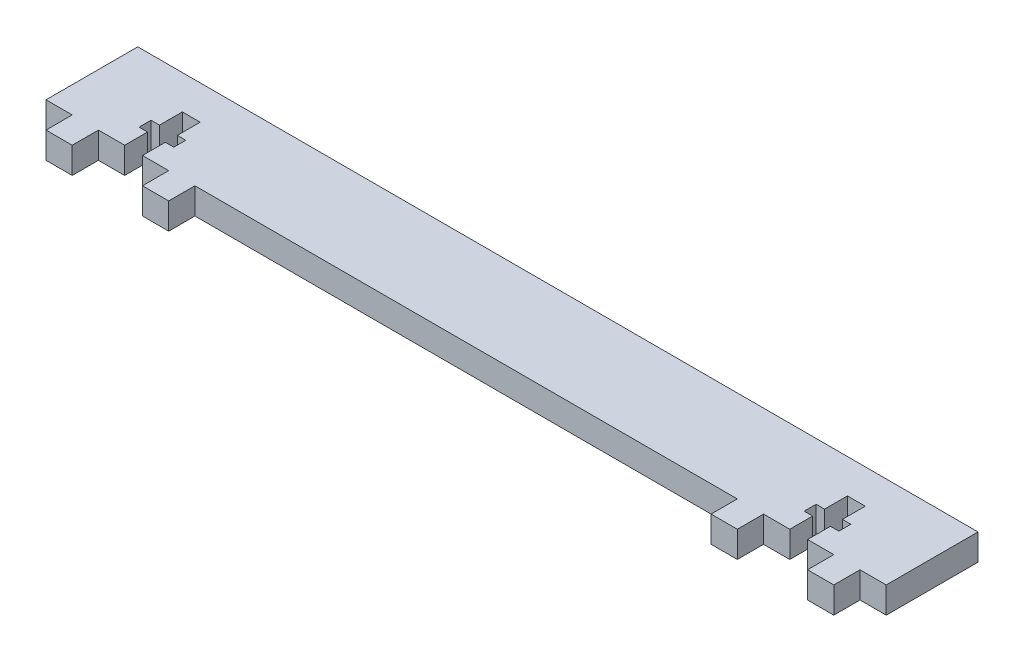
SolidWorks part; units mm, degrees
ref_plane "Front Plane" through (0, 0, 0) normal (0, 0, 1) x (1, 0, 0)
ref_plane "Top Plane" through (0, 0, 0) normal (0, 1, 0) x (1, 0, 0)
ref_plane "Right Plane" through (0, 0, 0) normal (1, 0, 0) x (0, 0, -1)
sketch "Sketch1" plane through (0, 0, 0) normal (0, 1, 0) x (1, 0, 0)
  line L0 (0, 11.1125) -> (0, -11.1125) construction
  line L1 (-101.7524, -11.1125) -> (-95.4024, -11.1125)
  line L2 (-101.7524, -11.1125) -> (-101.7524, 11.1125)
  line L3 (-101.7524, 11.1125) -> (101.7524, 11.1125)
  line L4 (101.7524, -11.1125) -> (101.7524, 11.1125)
  line L5 (-101.7524, -11.1125) -> (101.7524, 11.1125) construction
  line L6 (-101.7524, 11.1125) -> (101.7524, -11.1125) construction
  line L7 (-65.6844, -11.1125) -> (65.6844, -11.1125)
  line L8 (101.7524, -11.1125) -> (95.4024, -11.1125)
  point P0 (0, 0)
  line B0 (-89.0524, -11.1125) -> (-89.0524, -17.4625)
  line B1 (-89.0524, -17.4625) -> (-95.4024, -17.4625)
  line B2 (-95.4024, -17.4625) -> (-95.4024, -11.1125)
  line B3 (-82.7024, -11.1125) -> (-82.7024, -5.5775)
  line B4 (-82.7024, -5.5775) -> (-84.7434, -5.5775)
  line B5 (-84.7434, -5.5775) -> (-84.7434, -2.6775)
  line B6 (-84.7434, -2.6775) -> (-82.7024, -2.6775)
  line B7 (-82.7024, -2.6775) -> (-82.7024, 2.8575)
  line B8 (-82.7024, 2.8575) -> (-78.3844, 2.8575)
  line B9 (-78.3844, 2.8575) -> (-78.3844, -2.6775)
  line B10 (-78.3844, -2.6775) -> (-76.3434, -2.6775)
  line B11 (-76.3434, -2.6775) -> (-76.3434, -5.5775)
  line B12 (-76.3434, -5.5775) -> (-78.3844, -5.5775)
  line B13 (-78.3844, -5.5775) -> (-78.3844, -11.1125)
  line B14 (-80.5434, 2.8575) -> (-80.5434, -11.1125) construction
  line B15 (-72.0344, -11.1125) -> (-78.3844, -11.1125)
  line B16 (-65.6844, -17.4625) -> (-65.6844, -11.1125)
  line B17 (-89.0524, -11.1125) -> (-82.7024, -11.1125)
  line B18 (-72.0344, -17.4625) -> (-65.6844, -17.4625)
  line B19 (-72.0344, -11.1125) -> (-72.0344, -17.4625)
  line B20 (89.0524, -11.1125) -> (89.0524, -17.4625)
  line B21 (89.0524, -17.4625) -> (95.4024, -17.4625)
  line B22 (95.4024, -17.4625) -> (95.4024, -11.1125)
  line B23 (82.7024, -11.1125) -> (82.7024, -5.5775)
  line B24 (82.7024, -5.5775) -> (84.7434, -5.5775)
  line B25 (84.7434, -5.5775) -> (84.7434, -2.6775)
  line B26 (84.7434, -2.6775) -> (82.7024, -2.6775)
  line B27 (82.7024, -2.6775) -> (82.7024, 2.8575)
  line B28 (82.7024, 2.8575) -> (78.3844, 2.8575)
  line B29 (78.3844, 2.8575) -> (78.3844, -2.6775)
  line B30 (78.3844, -2.6775) -> (76.3434, -2.6775)
  line B31 (76.3434, -2.6775) -> (76.3434, -5.5775)
  line B32 (76.3434, -5.5775) -> (78.3844, -5.5775)
  line B33 (78.3844, -5.5775) -> (78.3844, -11.1125)
  line B34 (80.5434, 2.8575) -> (80.5434, -11.1125) construction
  line B35 (72.0344, -11.1125) -> (78.3844, -11.1125)
  line B36 (65.6844, -17.4625) -> (65.6844, -11.1125)
  line B37 (89.0524, -11.1125) -> (82.7024, -11.1125)
  line B38 (72.0344, -17.4625) -> (65.6844, -17.4625)
  line B39 (72.0344, -11.1125) -> (72.0344, -17.4625)
  dimension "D1" = 22.225
  dimension "D2" = 131.3688
  dimension "D3" = 6.35
sketch_block_instance "Male T-slot assembly-1"
sketch_block "Male T-slot assembly" parameters "D1"=6.35, "D2"=6.35, "D3"=4.318, "D4"=2.9, "D5"=8.4, "D6"=13.97, "D7"=6.35
sketch_block_instance "Male T-slot assembly-3"
extrude "Boss-Extrude1" add sketch "Sketch1" along normal blind 6.35 contours B39 B35 B33 B32 B31 B30 B29 B28 B27 B26 B25 B24 B23 B37 B20 B21 B22 L8 L4 L3 L2 L1 B2 B1 B0 B17 B3 B4 B5 B6 B7 B8 B9 B10 B11 B12 B13 B15 B19 B18 B16 L7 B36 B38 region at (0, 0, 0.3764)
equation "\"Ball Diameter\"= 1.75in"
equation "\"Ball Radius\" = \"Ball Diameter\"/2"
equation "\"Sheet Thickness\"= 0.25in"
equation "\"Screw Diameter\"= .17in"
equation "\"Robot Diameter\"= 14in"
equation "\"Castor Screw Diameter\"= 0.22in"
equation "\"Wheel Diameter\" = 4in"
equation "\"Nut Diameter\" = 8.4mm"
equation "\"Nut Height\" = 2.9mm"
equation "\"Screw Height\" = 0.55in"
equation "\"Pulley Diameter\" = 1in"
equation "\"Reactor Height\" = 14in"
equation "\"Elevator Height\" = 11.5in"
equation "\"Elevator Width\" = \"Ball Diameter\" + 0.25in"
equation "\"Elevator Bearing Diameter\" = sqr(2*(\"Sheet Thickness\"^2)) + 0.2in"
equation "\"Elevator Axle Endcap Diameter\" = \"Pulley Diameter\" + 0.25in"
equation "\"Elevator Axle Length\" = \"Elevator Width\" + 8*\"Sheet Thickness\""
equation "\"Elevator Clearance from Axis\" = 3.28in"
equation "\"Elevator Horizontal Clearance\" = \"Elevator Width\" + 0.5in"
equation "\"Claw Horizontal Seperation\" = (\"Elevator Width\"/2) - (1.5 * \"Sheet Thickness\") - 0.15in"
equation "\"Claw Radius\" = \"Ball Radius\" + 0.1in"
equation "\"Castor Wheel Height\" = 1.25in"
equation "\"Length of Chute\" = 8in"
equation "\"D1@Sketch1\"=\"Ball Radius\""
